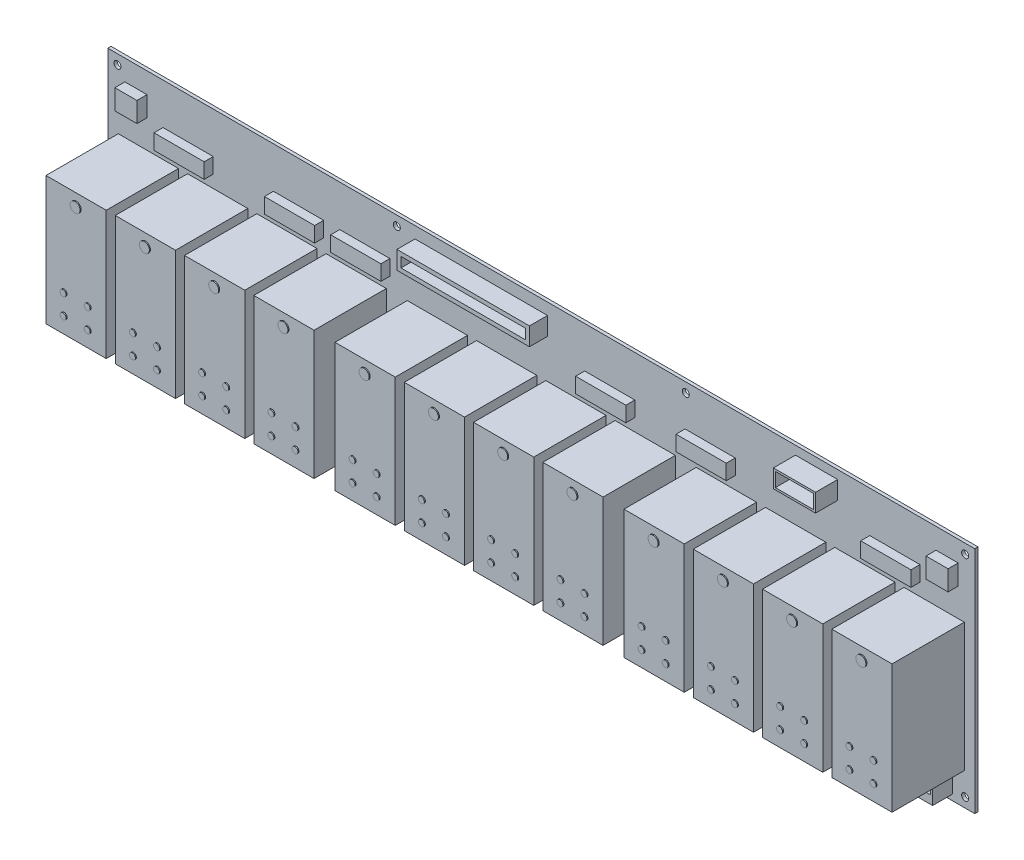
SolidWorks part; units mm, degrees
ref_plane "Front Plane" through (0, 0, 0) normal (0, 0, 1) x (1, 0, 0)
ref_plane "Top Plane" through (0, 0, 0) normal (0, 1, 0) x (1, 0, 0)
ref_plane "Right Plane" through (0, 0, 0) normal (1, 0, 0) x (0, 0, -1)
sketch "Sketch1" plane through (0, 0, 0) normal (0, 0, 1) x (1, 0, 0)
  line L1 (0, 0) -> (431.8, 0)
  line L2 (0, 0) -> (0, 114.3)
  line L3 (0, 114.3) -> (431.8, 114.3)
  line L4 (431.8, 0) -> (431.8, 114.3)
extrude "PCB" add sketch "Sketch1" along normal blind 1.6
ref_plane "Plane_z1_6" through (0, 0, 1.6) normal (0, 0, 1) x (1, 0, 0)
sketch "Sketch2" plane through (0, 0, 1.6) normal (0, 0, 1) x (1, 0, 0)
  line L1 (27.5, 86.2) -> (52.5, 86.2)
  line L2 (27.5, 86.2) -> (27.5, 93.8)
  line L3 (27.5, 93.8) -> (52.5, 93.8)
  line L4 (52.5, 86.2) -> (52.5, 93.8)
  line L6 (82.5, 86.2) -> (107.5, 86.2)
  line L7 (82.5, 86.2) -> (82.5, 93.8)
  line L8 (82.5, 93.8) -> (107.5, 93.8)
  line L9 (107.5, 86.2) -> (107.5, 93.8)
  line L11 (115.5, 86.2) -> (140.5, 86.2)
  line L12 (115.5, 86.2) -> (115.5, 93.8)
  line L13 (115.5, 93.8) -> (140.5, 93.8)
  line L14 (140.5, 86.2) -> (140.5, 93.8)
  line L16 (237.5, 86.2) -> (262.5, 86.2)
  line L17 (237.5, 86.2) -> (237.5, 93.8)
  line L18 (237.5, 93.8) -> (262.5, 93.8)
  line L19 (262.5, 86.2) -> (262.5, 93.8)
  line L21 (287.5, 86.2) -> (312.5, 86.2)
  line L22 (287.5, 86.2) -> (287.5, 93.8)
  line L23 (287.5, 93.8) -> (312.5, 93.8)
  line L24 (312.5, 86.2) -> (312.5, 93.8)
  line L26 (379.5, 86.2) -> (404.5, 86.2)
  line L27 (379.5, 86.2) -> (379.5, 93.8)
  line L28 (379.5, 93.8) -> (404.5, 93.8)
  line L29 (404.5, 86.2) -> (404.5, 93.8)
extrude "Body00" add sketch "Sketch2" along normal blind 4.5
sketch "Sketch3" plane through (0, 0, 1.6) normal (0, 0, 1) x (1, 0, 0)
  line L1 (8.5, 94) -> (19.5, 94)
  line L2 (8.5, 94) -> (8.5, 104)
  line L3 (8.5, 104) -> (19.5, 104)
  line L4 (19.5, 94) -> (19.5, 104)
  line L6 (412.5, 94) -> (423.5, 94)
  line L7 (412.5, 94) -> (412.5, 104)
  line L8 (412.5, 104) -> (423.5, 104)
  line L9 (423.5, 94) -> (423.5, 104)
extrude "Body01" add sketch "Sketch3" along normal blind 5
sketch "Sketch4" plane through (0, 0, 1.6) normal (0, 0, 1) x (1, 0, 0)
  line L1 (153, 99.5) -> (219, 99.5)
  line L2 (153, 99.5) -> (153, 108.5)
  line L3 (153, 108.5) -> (219, 108.5)
  line L4 (219, 99.5) -> (219, 108.5)
extrude "Body02" add sketch "Sketch4" along normal blind 9
sketch "Sketch5" plane through (0, 0, 1.6) normal (0, 0, 1) x (1, 0, 0)
  line L1 (11.007, 3) -> (132.927, 3)
  line L2 (11.007, 3) -> (11.007, 12)
  line L3 (11.007, 12) -> (132.927, 12)
  line L4 (132.927, 3) -> (132.927, 12)
  line L6 (154.94, 3) -> (276.86, 3)
  line L7 (154.94, 3) -> (154.94, 12)
  line L8 (154.94, 12) -> (276.86, 12)
  line L9 (276.86, 3) -> (276.86, 12)
  line L11 (298.873, 3) -> (420.793, 3)
  line L12 (298.873, 3) -> (298.873, 12)
  line L13 (298.873, 12) -> (420.793, 12)
  line L14 (420.793, 3) -> (420.793, 12)
extrude "Body03" add sketch "Sketch5" along normal blind 10
sketch "Sketch6" plane through (0, 0, 1.6) normal (0, 0, 1) x (1, 0, 0)
  line L1 (342.5, 101) -> (363.5, 101)
  line L2 (342.5, 101) -> (342.5, 110)
  line L3 (342.5, 110) -> (363.5, 110)
  line L4 (363.5, 101) -> (363.5, 110)
extrude "Body04" add sketch "Sketch6" along normal blind 11
sketch "Sketch7" plane through (0, 0, 1.6) normal (0, 0, 1) x (1, 0, 0)
  line L1 (5.217, 16) -> (35.217, 16)
  line L2 (5.217, 16) -> (5.217, 80)
  line L3 (5.217, 80) -> (35.217, 80)
  line L4 (35.217, 16) -> (35.217, 80)
  line L6 (39.717, 16) -> (69.717, 16)
  line L7 (39.717, 16) -> (39.717, 80)
  line L8 (39.717, 80) -> (69.717, 80)
  line L9 (69.717, 16) -> (69.717, 80)
  line L11 (74.217, 16) -> (104.217, 16)
  line L12 (74.217, 16) -> (74.217, 80)
  line L13 (74.217, 80) -> (104.217, 80)
  line L14 (104.217, 16) -> (104.217, 80)
  line L16 (108.717, 16) -> (138.717, 16)
  line L17 (108.717, 16) -> (108.717, 80)
  line L18 (108.717, 80) -> (138.717, 80)
  line L19 (138.717, 16) -> (138.717, 80)
  line L21 (149.15, 16) -> (179.15, 16)
  line L22 (149.15, 16) -> (149.15, 80)
  line L23 (149.15, 80) -> (179.15, 80)
  line L24 (179.15, 16) -> (179.15, 80)
  line L26 (183.65, 16) -> (213.65, 16)
  line L27 (183.65, 16) -> (183.65, 80)
  line L28 (183.65, 80) -> (213.65, 80)
  line L29 (213.65, 16) -> (213.65, 80)
  line L31 (218.15, 16) -> (248.15, 16)
  line L32 (218.15, 16) -> (218.15, 80)
  line L33 (218.15, 80) -> (248.15, 80)
  line L34 (248.15, 16) -> (248.15, 80)
  line L36 (252.65, 16) -> (282.65, 16)
  line L37 (252.65, 16) -> (252.65, 80)
  line L38 (252.65, 80) -> (282.65, 80)
  line L39 (282.65, 16) -> (282.65, 80)
  line L41 (293.083, 16) -> (323.083, 16)
  line L42 (293.083, 16) -> (293.083, 80)
  line L43 (293.083, 80) -> (323.083, 80)
  line L44 (323.083, 16) -> (323.083, 80)
  line L46 (327.583, 16) -> (357.583, 16)
  line L47 (327.583, 16) -> (327.583, 80)
  line L48 (327.583, 80) -> (357.583, 80)
  line L49 (357.583, 16) -> (357.583, 80)
  line L51 (362.083, 16) -> (392.083, 16)
  line L52 (362.083, 16) -> (362.083, 80)
  line L53 (362.083, 80) -> (392.083, 80)
  line L54 (392.083, 16) -> (392.083, 80)
  line L56 (396.583, 16) -> (426.583, 16)
  line L57 (396.583, 16) -> (396.583, 80)
  line L58 (396.583, 80) -> (426.583, 80)
  line L59 (426.583, 16) -> (426.583, 80)
extrude "Body05" add sketch "Sketch7" along normal blind 36
ref_plane "Plane_z37_6" through (0, 0, 37.6) normal (0, 0, 1) x (1, 0, 0)
sketch "Sketch8" plane through (0, 0, 37.6) normal (0, 0, 1) x (1, 0, 0)
  circle A0 centre (14.217, 24) radius 1.5
  circle A1 centre (14.217, 34) radius 1.5
  circle A2 centre (26.217, 24) radius 1.5
  circle A3 centre (26.217, 34) radius 1.5
  circle A4 centre (20.217, 74) radius 2.5
  circle A5 centre (48.717, 24) radius 1.5
  circle A6 centre (48.717, 34) radius 1.5
  circle A7 centre (60.717, 24) radius 1.5
  circle A8 centre (60.717, 34) radius 1.5
  circle A9 centre (54.717, 74) radius 2.5
  circle A10 centre (83.217, 24) radius 1.5
  circle A11 centre (83.217, 34) radius 1.5
  circle A12 centre (95.217, 24) radius 1.5
  circle A13 centre (95.217, 34) radius 1.5
  circle A14 centre (89.217, 74) radius 2.5
  circle A15 centre (117.717, 24) radius 1.5
  circle A16 centre (117.717, 34) radius 1.5
  circle A17 centre (129.717, 24) radius 1.5
  circle A18 centre (129.717, 34) radius 1.5
  circle A19 centre (123.717, 74) radius 2.5
  circle A20 centre (158.15, 24) radius 1.5
  circle A21 centre (158.15, 34) radius 1.5
  circle A22 centre (170.15, 24) radius 1.5
  circle A23 centre (170.15, 34) radius 1.5
  circle A24 centre (164.15, 74) radius 2.5
  circle A25 centre (192.65, 24) radius 1.5
  circle A26 centre (192.65, 34) radius 1.5
  circle A27 centre (204.65, 24) radius 1.5
  circle A28 centre (204.65, 34) radius 1.5
  circle A29 centre (198.65, 74) radius 2.5
  circle A30 centre (227.15, 24) radius 1.5
  circle A31 centre (227.15, 34) radius 1.5
  circle A32 centre (239.15, 24) radius 1.5
  circle A33 centre (239.15, 34) radius 1.5
  circle A34 centre (233.15, 74) radius 2.5
  circle A35 centre (261.65, 24) radius 1.5
  circle A36 centre (261.65, 34) radius 1.5
  circle A37 centre (273.65, 24) radius 1.5
  circle A38 centre (273.65, 34) radius 1.5
  circle A39 centre (267.65, 74) radius 2.5
  circle A40 centre (302.083, 24) radius 1.5
  circle A41 centre (302.083, 34) radius 1.5
  circle A42 centre (314.083, 24) radius 1.5
  circle A43 centre (314.083, 34) radius 1.5
  circle A44 centre (308.083, 74) radius 2.5
  circle A45 centre (336.583, 24) radius 1.5
  circle A46 centre (336.583, 34) radius 1.5
  circle A47 centre (348.583, 24) radius 1.5
  circle A48 centre (348.583, 34) radius 1.5
  circle A49 centre (342.583, 74) radius 2.5
  circle A50 centre (371.083, 24) radius 1.5
  circle A51 centre (371.083, 34) radius 1.5
  circle A52 centre (383.083, 24) radius 1.5
  circle A53 centre (383.083, 34) radius 1.5
  circle A54 centre (377.083, 74) radius 2.5
  circle A55 centre (405.583, 24) radius 1.5
  circle A56 centre (405.583, 34) radius 1.5
  circle A57 centre (417.583, 24) radius 1.5
  circle A58 centre (417.583, 34) radius 1.5
  circle A59 centre (411.583, 74) radius 2.5
extrude "Body06" add sketch "Sketch8" along normal blind 0.5
ref_plane "Plane_y7" through (0, 7, 0) normal (0, 1, 0) x (1, 0, 0)
sketch "Sketch9" plane through (0, 7, 0) normal (0, 1, 0) x (1, 0, 0)
  line L1 (11.947, -3.5) -> (15.147, -3.5)
  line L2 (11.947, -3.5) -> (11.947, -6.7)
  line L3 (11.947, -6.7) -> (15.147, -6.7)
  line L4 (15.147, -3.5) -> (15.147, -6.7)
  line L6 (17.027, -3.5) -> (20.227, -3.5)
  line L7 (17.027, -3.5) -> (17.027, -6.7)
  line L8 (17.027, -6.7) -> (20.227, -6.7)
  line L9 (20.227, -3.5) -> (20.227, -6.7)
  line L11 (22.107, -3.5) -> (25.307, -3.5)
  line L12 (22.107, -3.5) -> (22.107, -6.7)
  line L13 (22.107, -6.7) -> (25.307, -6.7)
  line L14 (25.307, -3.5) -> (25.307, -6.7)
  line L16 (27.187, -3.5) -> (30.387, -3.5)
  line L17 (27.187, -3.5) -> (27.187, -6.7)
  line L18 (27.187, -6.7) -> (30.387, -6.7)
  line L19 (30.387, -3.5) -> (30.387, -6.7)
  line L21 (32.267, -3.5) -> (35.467, -3.5)
  line L22 (32.267, -3.5) -> (32.267, -6.7)
  line L23 (32.267, -6.7) -> (35.467, -6.7)
  line L24 (35.467, -3.5) -> (35.467, -6.7)
  line L26 (37.347, -3.5) -> (40.547, -3.5)
  line L27 (37.347, -3.5) -> (37.347, -6.7)
  line L28 (37.347, -6.7) -> (40.547, -6.7)
  line L29 (40.547, -3.5) -> (40.547, -6.7)
  line L31 (42.427, -3.5) -> (45.627, -3.5)
  line L32 (42.427, -3.5) -> (42.427, -6.7)
  line L33 (42.427, -6.7) -> (45.627, -6.7)
  line L34 (45.627, -3.5) -> (45.627, -6.7)
  line L36 (47.507, -3.5) -> (50.707, -3.5)
  line L37 (47.507, -3.5) -> (47.507, -6.7)
  line L38 (47.507, -6.7) -> (50.707, -6.7)
  line L39 (50.707, -3.5) -> (50.707, -6.7)
  line L41 (52.587, -3.5) -> (55.787, -3.5)
  line L42 (52.587, -3.5) -> (52.587, -6.7)
  line L43 (52.587, -6.7) -> (55.787, -6.7)
  line L44 (55.787, -3.5) -> (55.787, -6.7)
  line L46 (57.667, -3.5) -> (60.867, -3.5)
  line L47 (57.667, -3.5) -> (57.667, -6.7)
  line L48 (57.667, -6.7) -> (60.867, -6.7)
  line L49 (60.867, -3.5) -> (60.867, -6.7)
  line L51 (62.747, -3.5) -> (65.947, -3.5)
  line L52 (62.747, -3.5) -> (62.747, -6.7)
  line L53 (62.747, -6.7) -> (65.947, -6.7)
  line L54 (65.947, -3.5) -> (65.947, -6.7)
  line L56 (67.827, -3.5) -> (71.027, -3.5)
  line L57 (67.827, -3.5) -> (67.827, -6.7)
  line L58 (67.827, -6.7) -> (71.027, -6.7)
  line L59 (71.027, -3.5) -> (71.027, -6.7)
  line L61 (72.907, -3.5) -> (76.107, -3.5)
  line L62 (72.907, -3.5) -> (72.907, -6.7)
  line L63 (72.907, -6.7) -> (76.107, -6.7)
  line L64 (76.107, -3.5) -> (76.107, -6.7)
  line L66 (77.987, -3.5) -> (81.187, -3.5)
  line L67 (77.987, -3.5) -> (77.987, -6.7)
  line L68 (77.987, -6.7) -> (81.187, -6.7)
  line L69 (81.187, -3.5) -> (81.187, -6.7)
  line L71 (83.067, -3.5) -> (86.267, -3.5)
  line L72 (83.067, -3.5) -> (83.067, -6.7)
  line L73 (83.067, -6.7) -> (86.267, -6.7)
  line L74 (86.267, -3.5) -> (86.267, -6.7)
  line L76 (88.147, -3.5) -> (91.347, -3.5)
  line L77 (88.147, -3.5) -> (88.147, -6.7)
  line L78 (88.147, -6.7) -> (91.347, -6.7)
  line L79 (91.347, -3.5) -> (91.347, -6.7)
  line L81 (93.227, -3.5) -> (96.427, -3.5)
  line L82 (93.227, -3.5) -> (93.227, -6.7)
  line L83 (93.227, -6.7) -> (96.427, -6.7)
  line L84 (96.427, -3.5) -> (96.427, -6.7)
  line L86 (98.307, -3.5) -> (101.507, -3.5)
  line L87 (98.307, -3.5) -> (98.307, -6.7)
  line L88 (98.307, -6.7) -> (101.507, -6.7)
  line L89 (101.507, -3.5) -> (101.507, -6.7)
  line L91 (103.387, -3.5) -> (106.587, -3.5)
  line L92 (103.387, -3.5) -> (103.387, -6.7)
  line L93 (103.387, -6.7) -> (106.587, -6.7)
  line L94 (106.587, -3.5) -> (106.587, -6.7)
  line L96 (108.467, -3.5) -> (111.667, -3.5)
  line L97 (108.467, -3.5) -> (108.467, -6.7)
  line L98 (108.467, -6.7) -> (111.667, -6.7)
  line L99 (111.667, -3.5) -> (111.667, -6.7)
  line L101 (113.547, -3.5) -> (116.747, -3.5)
  line L102 (113.547, -3.5) -> (113.547, -6.7)
  line L103 (113.547, -6.7) -> (116.747, -6.7)
  line L104 (116.747, -3.5) -> (116.747, -6.7)
  line L106 (118.627, -3.5) -> (121.827, -3.5)
  line L107 (118.627, -3.5) -> (118.627, -6.7)
  line L108 (118.627, -6.7) -> (121.827, -6.7)
  line L109 (121.827, -3.5) -> (121.827, -6.7)
  line L111 (123.707, -3.5) -> (126.907, -3.5)
  line L112 (123.707, -3.5) -> (123.707, -6.7)
  line L113 (123.707, -6.7) -> (126.907, -6.7)
  line L114 (126.907, -3.5) -> (126.907, -6.7)
  line L116 (128.787, -3.5) -> (131.987, -3.5)
  line L117 (128.787, -3.5) -> (128.787, -6.7)
  line L118 (128.787, -6.7) -> (131.987, -6.7)
  line L119 (131.987, -3.5) -> (131.987, -6.7)
  line L121 (155.88, -3.5) -> (159.08, -3.5)
  line L122 (155.88, -3.5) -> (155.88, -6.7)
  line L123 (155.88, -6.7) -> (159.08, -6.7)
  line L124 (159.08, -3.5) -> (159.08, -6.7)
  line L126 (160.96, -3.5) -> (164.16, -3.5)
  line L127 (160.96, -3.5) -> (160.96, -6.7)
  line L128 (160.96, -6.7) -> (164.16, -6.7)
  line L129 (164.16, -3.5) -> (164.16, -6.7)
  line L131 (166.04, -3.5) -> (169.24, -3.5)
  line L132 (166.04, -3.5) -> (166.04, -6.7)
  line L133 (166.04, -6.7) -> (169.24, -6.7)
  line L134 (169.24, -3.5) -> (169.24, -6.7)
  line L136 (171.12, -3.5) -> (174.32, -3.5)
  line L137 (171.12, -3.5) -> (171.12, -6.7)
  line L138 (171.12, -6.7) -> (174.32, -6.7)
  line L139 (174.32, -3.5) -> (174.32, -6.7)
  line L141 (176.2, -3.5) -> (179.4, -3.5)
  line L142 (176.2, -3.5) -> (176.2, -6.7)
  line L143 (176.2, -6.7) -> (179.4, -6.7)
  line L144 (179.4, -3.5) -> (179.4, -6.7)
  line L146 (181.28, -3.5) -> (184.48, -3.5)
  line L147 (181.28, -3.5) -> (181.28, -6.7)
  line L148 (181.28, -6.7) -> (184.48, -6.7)
  line L149 (184.48, -3.5) -> (184.48, -6.7)
  line L151 (186.36, -3.5) -> (189.56, -3.5)
  line L152 (186.36, -3.5) -> (186.36, -6.7)
  line L153 (186.36, -6.7) -> (189.56, -6.7)
  line L154 (189.56, -3.5) -> (189.56, -6.7)
  line L156 (191.44, -3.5) -> (194.64, -3.5)
  line L157 (191.44, -3.5) -> (191.44, -6.7)
  line L158 (191.44, -6.7) -> (194.64, -6.7)
  line L159 (194.64, -3.5) -> (194.64, -6.7)
  line L161 (196.52, -3.5) -> (199.72, -3.5)
  line L162 (196.52, -3.5) -> (196.52, -6.7)
  line L163 (196.52, -6.7) -> (199.72, -6.7)
  line L164 (199.72, -3.5) -> (199.72, -6.7)
  line L166 (201.6, -3.5) -> (204.8, -3.5)
  line L167 (201.6, -3.5) -> (201.6, -6.7)
  line L168 (201.6, -6.7) -> (204.8, -6.7)
  line L169 (204.8, -3.5) -> (204.8, -6.7)
  line L171 (206.68, -3.5) -> (209.88, -3.5)
  line L172 (206.68, -3.5) -> (206.68, -6.7)
  line L173 (206.68, -6.7) -> (209.88, -6.7)
  line L174 (209.88, -3.5) -> (209.88, -6.7)
  line L176 (211.76, -3.5) -> (214.96, -3.5)
  line L177 (211.76, -3.5) -> (211.76, -6.7)
  line L178 (211.76, -6.7) -> (214.96, -6.7)
  line L179 (214.96, -3.5) -> (214.96, -6.7)
  line L181 (216.84, -3.5) -> (220.04, -3.5)
  line L182 (216.84, -3.5) -> (216.84, -6.7)
  line L183 (216.84, -6.7) -> (220.04, -6.7)
  line L184 (220.04, -3.5) -> (220.04, -6.7)
  line L186 (221.92, -3.5) -> (225.12, -3.5)
  line L187 (221.92, -3.5) -> (221.92, -6.7)
  line L188 (221.92, -6.7) -> (225.12, -6.7)
  line L189 (225.12, -3.5) -> (225.12, -6.7)
  line L191 (227, -3.5) -> (230.2, -3.5)
  line L192 (227, -3.5) -> (227, -6.7)
  line L193 (227, -6.7) -> (230.2, -6.7)
  line L194 (230.2, -3.5) -> (230.2, -6.7)
  line L196 (232.08, -3.5) -> (235.28, -3.5)
  line L197 (232.08, -3.5) -> (232.08, -6.7)
  line L198 (232.08, -6.7) -> (235.28, -6.7)
  line L199 (235.28, -3.5) -> (235.28, -6.7)
  line L201 (237.16, -3.5) -> (240.36, -3.5)
  line L202 (237.16, -3.5) -> (237.16, -6.7)
  line L203 (237.16, -6.7) -> (240.36, -6.7)
  line L204 (240.36, -3.5) -> (240.36, -6.7)
  line L206 (242.24, -3.5) -> (245.44, -3.5)
  line L207 (242.24, -3.5) -> (242.24, -6.7)
  line L208 (242.24, -6.7) -> (245.44, -6.7)
  line L209 (245.44, -3.5) -> (245.44, -6.7)
  line L211 (247.32, -3.5) -> (250.52, -3.5)
  line L212 (247.32, -3.5) -> (247.32, -6.7)
  line L213 (247.32, -6.7) -> (250.52, -6.7)
  line L214 (250.52, -3.5) -> (250.52, -6.7)
  line L216 (252.4, -3.5) -> (255.6, -3.5)
  line L217 (252.4, -3.5) -> (252.4, -6.7)
  line L218 (252.4, -6.7) -> (255.6, -6.7)
  line L219 (255.6, -3.5) -> (255.6, -6.7)
  line L221 (257.48, -3.5) -> (260.68, -3.5)
  line L222 (257.48, -3.5) -> (257.48, -6.7)
  line L223 (257.48, -6.7) -> (260.68, -6.7)
  line L224 (260.68, -3.5) -> (260.68, -6.7)
  line L226 (262.56, -3.5) -> (265.76, -3.5)
  line L227 (262.56, -3.5) -> (262.56, -6.7)
  line L228 (262.56, -6.7) -> (265.76, -6.7)
  line L229 (265.76, -3.5) -> (265.76, -6.7)
  line L231 (267.64, -3.5) -> (270.84, -3.5)
  line L232 (267.64, -3.5) -> (267.64, -6.7)
  line L233 (267.64, -6.7) -> (270.84, -6.7)
  line L234 (270.84, -3.5) -> (270.84, -6.7)
  line L236 (272.72, -3.5) -> (275.92, -3.5)
  line L237 (272.72, -3.5) -> (272.72, -6.7)
  line L238 (272.72, -6.7) -> (275.92, -6.7)
  line L239 (275.92, -3.5) -> (275.92, -6.7)
  line L241 (299.813, -3.5) -> (303.013, -3.5)
  line L242 (299.813, -3.5) -> (299.813, -6.7)
  line L243 (299.813, -6.7) -> (303.013, -6.7)
  line L244 (303.013, -3.5) -> (303.013, -6.7)
  line L246 (304.893, -3.5) -> (308.093, -3.5)
  line L247 (304.893, -3.5) -> (304.893, -6.7)
  line L248 (304.893, -6.7) -> (308.093, -6.7)
  line L249 (308.093, -3.5) -> (308.093, -6.7)
  line L251 (309.973, -3.5) -> (313.173, -3.5)
  line L252 (309.973, -3.5) -> (309.973, -6.7)
  line L253 (309.973, -6.7) -> (313.173, -6.7)
  line L254 (313.173, -3.5) -> (313.173, -6.7)
  line L256 (315.053, -3.5) -> (318.253, -3.5)
  line L257 (315.053, -3.5) -> (315.053, -6.7)
  line L258 (315.053, -6.7) -> (318.253, -6.7)
  line L259 (318.253, -3.5) -> (318.253, -6.7)
  line L261 (320.133, -3.5) -> (323.333, -3.5)
  line L262 (320.133, -3.5) -> (320.133, -6.7)
  line L263 (320.133, -6.7) -> (323.333, -6.7)
  line L264 (323.333, -3.5) -> (323.333, -6.7)
  line L266 (325.213, -3.5) -> (328.413, -3.5)
  line L267 (325.213, -3.5) -> (325.213, -6.7)
  line L268 (325.213, -6.7) -> (328.413, -6.7)
  line L269 (328.413, -3.5) -> (328.413, -6.7)
  line L271 (330.293, -3.5) -> (333.493, -3.5)
  line L272 (330.293, -3.5) -> (330.293, -6.7)
  line L273 (330.293, -6.7) -> (333.493, -6.7)
  line L274 (333.493, -3.5) -> (333.493, -6.7)
  line L276 (335.373, -3.5) -> (338.573, -3.5)
  line L277 (335.373, -3.5) -> (335.373, -6.7)
  line L278 (335.373, -6.7) -> (338.573, -6.7)
  line L279 (338.573, -3.5) -> (338.573, -6.7)
  line L281 (340.453, -3.5) -> (343.653, -3.5)
  line L282 (340.453, -3.5) -> (340.453, -6.7)
  line L283 (340.453, -6.7) -> (343.653, -6.7)
  line L284 (343.653, -3.5) -> (343.653, -6.7)
  line L286 (345.533, -3.5) -> (348.733, -3.5)
  line L287 (345.533, -3.5) -> (345.533, -6.7)
  line L288 (345.533, -6.7) -> (348.733, -6.7)
  line L289 (348.733, -3.5) -> (348.733, -6.7)
  line L291 (350.613, -3.5) -> (353.813, -3.5)
  line L292 (350.613, -3.5) -> (350.613, -6.7)
  line L293 (350.613, -6.7) -> (353.813, -6.7)
  line L294 (353.813, -3.5) -> (353.813, -6.7)
  line L296 (355.693, -3.5) -> (358.893, -3.5)
  line L297 (355.693, -3.5) -> (355.693, -6.7)
  line L298 (355.693, -6.7) -> (358.893, -6.7)
  line L299 (358.893, -3.5) -> (358.893, -6.7)
  line L301 (360.773, -3.5) -> (363.973, -3.5)
  line L302 (360.773, -3.5) -> (360.773, -6.7)
  line L303 (360.773, -6.7) -> (363.973, -6.7)
  line L304 (363.973, -3.5) -> (363.973, -6.7)
  line L306 (365.853, -3.5) -> (369.053, -3.5)
  line L307 (365.853, -3.5) -> (365.853, -6.7)
  line L308 (365.853, -6.7) -> (369.053, -6.7)
  line L309 (369.053, -3.5) -> (369.053, -6.7)
  line L311 (370.933, -3.5) -> (374.133, -3.5)
  line L312 (370.933, -3.5) -> (370.933, -6.7)
  line L313 (370.933, -6.7) -> (374.133, -6.7)
  line L314 (374.133, -3.5) -> (374.133, -6.7)
  line L316 (376.013, -3.5) -> (379.213, -3.5)
  line L317 (376.013, -3.5) -> (376.013, -6.7)
  line L318 (376.013, -6.7) -> (379.213, -6.7)
  line L319 (379.213, -3.5) -> (379.213, -6.7)
  line L321 (381.093, -3.5) -> (384.293, -3.5)
  line L322 (381.093, -3.5) -> (381.093, -6.7)
  line L323 (381.093, -6.7) -> (384.293, -6.7)
  line L324 (384.293, -3.5) -> (384.293, -6.7)
  line L326 (386.173, -3.5) -> (389.373, -3.5)
  line L327 (386.173, -3.5) -> (386.173, -6.7)
  line L328 (386.173, -6.7) -> (389.373, -6.7)
  line L329 (389.373, -3.5) -> (389.373, -6.7)
  line L331 (391.253, -3.5) -> (394.453, -3.5)
  line L332 (391.253, -3.5) -> (391.253, -6.7)
  line L333 (391.253, -6.7) -> (394.453, -6.7)
  line L334 (394.453, -3.5) -> (394.453, -6.7)
  line L336 (396.333, -3.5) -> (399.533, -3.5)
  line L337 (396.333, -3.5) -> (396.333, -6.7)
  line L338 (396.333, -6.7) -> (399.533, -6.7)
  line L339 (399.533, -3.5) -> (399.533, -6.7)
  line L341 (401.413, -3.5) -> (404.613, -3.5)
  line L342 (401.413, -3.5) -> (401.413, -6.7)
  line L343 (401.413, -6.7) -> (404.613, -6.7)
  line L344 (404.613, -3.5) -> (404.613, -6.7)
  line L346 (406.493, -3.5) -> (409.693, -3.5)
  line L347 (406.493, -3.5) -> (406.493, -6.7)
  line L348 (406.493, -6.7) -> (409.693, -6.7)
  line L349 (409.693, -3.5) -> (409.693, -6.7)
  line L351 (411.573, -3.5) -> (414.773, -3.5)
  line L352 (411.573, -3.5) -> (411.573, -6.7)
  line L353 (411.573, -6.7) -> (414.773, -6.7)
  line L354 (414.773, -3.5) -> (414.773, -6.7)
  line L356 (416.653, -3.5) -> (419.853, -3.5)
  line L357 (416.653, -3.5) -> (416.653, -6.7)
  line L358 (416.653, -6.7) -> (419.853, -6.7)
  line L359 (419.853, -3.5) -> (419.853, -6.7)
extrude "Cut00" cut sketch "Sketch9" against normal blind 4
ref_plane "Plane_z10_6" through (0, 0, 10.6) normal (0, 0, 1) x (1, 0, 0)
sketch "Sketch10" plane through (0, 0, 10.6) normal (0, 0, 1) x (1, 0, 0)
  line L1 (155, 101.5) -> (217, 101.5)
  line L2 (155, 101.5) -> (155, 106.5)
  line L3 (155, 106.5) -> (217, 106.5)
  line L4 (217, 101.5) -> (217, 106.5)
extrude "Cut01" cut sketch "Sketch10" against normal blind 7
ref_plane "Plane_z11_6" through (0, 0, 11.6) normal (0, 0, 1) x (1, 0, 0)
sketch "Sketch11" plane through (0, 0, 11.6) normal (0, 0, 1) x (1, 0, 0)
  line L1 (12.147, 7.1) -> (14.947, 7.1)
  line L2 (12.147, 7.1) -> (12.147, 9.9)
  line L3 (12.147, 9.9) -> (14.947, 9.9)
  line L4 (14.947, 7.1) -> (14.947, 9.9)
  line L6 (17.227, 7.1) -> (20.027, 7.1)
  line L7 (17.227, 7.1) -> (17.227, 9.9)
  line L8 (17.227, 9.9) -> (20.027, 9.9)
  line L9 (20.027, 7.1) -> (20.027, 9.9)
  line L11 (22.307, 7.1) -> (25.107, 7.1)
  line L12 (22.307, 7.1) -> (22.307, 9.9)
  line L13 (22.307, 9.9) -> (25.107, 9.9)
  line L14 (25.107, 7.1) -> (25.107, 9.9)
  line L16 (27.387, 7.1) -> (30.187, 7.1)
  line L17 (27.387, 7.1) -> (27.387, 9.9)
  line L18 (27.387, 9.9) -> (30.187, 9.9)
  line L19 (30.187, 7.1) -> (30.187, 9.9)
  line L21 (32.467, 7.1) -> (35.267, 7.1)
  line L22 (32.467, 7.1) -> (32.467, 9.9)
  line L23 (32.467, 9.9) -> (35.267, 9.9)
  line L24 (35.267, 7.1) -> (35.267, 9.9)
  line L26 (37.547, 7.1) -> (40.347, 7.1)
  line L27 (37.547, 7.1) -> (37.547, 9.9)
  line L28 (37.547, 9.9) -> (40.347, 9.9)
  line L29 (40.347, 7.1) -> (40.347, 9.9)
  line L31 (42.627, 7.1) -> (45.427, 7.1)
  line L32 (42.627, 7.1) -> (42.627, 9.9)
  line L33 (42.627, 9.9) -> (45.427, 9.9)
  line L34 (45.427, 7.1) -> (45.427, 9.9)
  line L36 (47.707, 7.1) -> (50.507, 7.1)
  line L37 (47.707, 7.1) -> (47.707, 9.9)
  line L38 (47.707, 9.9) -> (50.507, 9.9)
  line L39 (50.507, 7.1) -> (50.507, 9.9)
  line L41 (52.787, 7.1) -> (55.587, 7.1)
  line L42 (52.787, 7.1) -> (52.787, 9.9)
  line L43 (52.787, 9.9) -> (55.587, 9.9)
  line L44 (55.587, 7.1) -> (55.587, 9.9)
  line L46 (57.867, 7.1) -> (60.667, 7.1)
  line L47 (57.867, 7.1) -> (57.867, 9.9)
  line L48 (57.867, 9.9) -> (60.667, 9.9)
  line L49 (60.667, 7.1) -> (60.667, 9.9)
  line L51 (62.947, 7.1) -> (65.747, 7.1)
  line L52 (62.947, 7.1) -> (62.947, 9.9)
  line L53 (62.947, 9.9) -> (65.747, 9.9)
  line L54 (65.747, 7.1) -> (65.747, 9.9)
  line L56 (68.027, 7.1) -> (70.827, 7.1)
  line L57 (68.027, 7.1) -> (68.027, 9.9)
  line L58 (68.027, 9.9) -> (70.827, 9.9)
  line L59 (70.827, 7.1) -> (70.827, 9.9)
  line L61 (73.107, 7.1) -> (75.907, 7.1)
  line L62 (73.107, 7.1) -> (73.107, 9.9)
  line L63 (73.107, 9.9) -> (75.907, 9.9)
  line L64 (75.907, 7.1) -> (75.907, 9.9)
  line L66 (78.187, 7.1) -> (80.987, 7.1)
  line L67 (78.187, 7.1) -> (78.187, 9.9)
  line L68 (78.187, 9.9) -> (80.987, 9.9)
  line L69 (80.987, 7.1) -> (80.987, 9.9)
  line L71 (83.267, 7.1) -> (86.067, 7.1)
  line L72 (83.267, 7.1) -> (83.267, 9.9)
  line L73 (83.267, 9.9) -> (86.067, 9.9)
  line L74 (86.067, 7.1) -> (86.067, 9.9)
  line L76 (88.347, 7.1) -> (91.147, 7.1)
  line L77 (88.347, 7.1) -> (88.347, 9.9)
  line L78 (88.347, 9.9) -> (91.147, 9.9)
  line L79 (91.147, 7.1) -> (91.147, 9.9)
  line L81 (93.427, 7.1) -> (96.227, 7.1)
  line L82 (93.427, 7.1) -> (93.427, 9.9)
  line L83 (93.427, 9.9) -> (96.227, 9.9)
  line L84 (96.227, 7.1) -> (96.227, 9.9)
  line L86 (98.507, 7.1) -> (101.307, 7.1)
  line L87 (98.507, 7.1) -> (98.507, 9.9)
  line L88 (98.507, 9.9) -> (101.307, 9.9)
  line L89 (101.307, 7.1) -> (101.307, 9.9)
  line L91 (103.587, 7.1) -> (106.387, 7.1)
  line L92 (103.587, 7.1) -> (103.587, 9.9)
  line L93 (103.587, 9.9) -> (106.387, 9.9)
  line L94 (106.387, 7.1) -> (106.387, 9.9)
  line L96 (108.667, 7.1) -> (111.467, 7.1)
  line L97 (108.667, 7.1) -> (108.667, 9.9)
  line L98 (108.667, 9.9) -> (111.467, 9.9)
  line L99 (111.467, 7.1) -> (111.467, 9.9)
  line L101 (113.747, 7.1) -> (116.547, 7.1)
  line L102 (113.747, 7.1) -> (113.747, 9.9)
  line L103 (113.747, 9.9) -> (116.547, 9.9)
  line L104 (116.547, 7.1) -> (116.547, 9.9)
  line L106 (118.827, 7.1) -> (121.627, 7.1)
  line L107 (118.827, 7.1) -> (118.827, 9.9)
  line L108 (118.827, 9.9) -> (121.627, 9.9)
  line L109 (121.627, 7.1) -> (121.627, 9.9)
  line L111 (123.907, 7.1) -> (126.707, 7.1)
  line L112 (123.907, 7.1) -> (123.907, 9.9)
  line L113 (123.907, 9.9) -> (126.707, 9.9)
  line L114 (126.707, 7.1) -> (126.707, 9.9)
  line L116 (128.987, 7.1) -> (131.787, 7.1)
  line L117 (128.987, 7.1) -> (128.987, 9.9)
  line L118 (128.987, 9.9) -> (131.787, 9.9)
  line L119 (131.787, 7.1) -> (131.787, 9.9)
  line L121 (156.08, 7.1) -> (158.88, 7.1)
  line L122 (156.08, 7.1) -> (156.08, 9.9)
  line L123 (156.08, 9.9) -> (158.88, 9.9)
  line L124 (158.88, 7.1) -> (158.88, 9.9)
  line L126 (161.16, 7.1) -> (163.96, 7.1)
  line L127 (161.16, 7.1) -> (161.16, 9.9)
  line L128 (161.16, 9.9) -> (163.96, 9.9)
  line L129 (163.96, 7.1) -> (163.96, 9.9)
  line L131 (166.24, 7.1) -> (169.04, 7.1)
  line L132 (166.24, 7.1) -> (166.24, 9.9)
  line L133 (166.24, 9.9) -> (169.04, 9.9)
  line L134 (169.04, 7.1) -> (169.04, 9.9)
  line L136 (171.32, 7.1) -> (174.12, 7.1)
  line L137 (171.32, 7.1) -> (171.32, 9.9)
  line L138 (171.32, 9.9) -> (174.12, 9.9)
  line L139 (174.12, 7.1) -> (174.12, 9.9)
  line L141 (176.4, 7.1) -> (179.2, 7.1)
  line L142 (176.4, 7.1) -> (176.4, 9.9)
  line L143 (176.4, 9.9) -> (179.2, 9.9)
  line L144 (179.2, 7.1) -> (179.2, 9.9)
  line L146 (181.48, 7.1) -> (184.28, 7.1)
  line L147 (181.48, 7.1) -> (181.48, 9.9)
  line L148 (181.48, 9.9) -> (184.28, 9.9)
  line L149 (184.28, 7.1) -> (184.28, 9.9)
  line L151 (186.56, 7.1) -> (189.36, 7.1)
  line L152 (186.56, 7.1) -> (186.56, 9.9)
  line L153 (186.56, 9.9) -> (189.36, 9.9)
  line L154 (189.36, 7.1) -> (189.36, 9.9)
  line L156 (191.64, 7.1) -> (194.44, 7.1)
  line L157 (191.64, 7.1) -> (191.64, 9.9)
  line L158 (191.64, 9.9) -> (194.44, 9.9)
  line L159 (194.44, 7.1) -> (194.44, 9.9)
  line L161 (196.72, 7.1) -> (199.52, 7.1)
  line L162 (196.72, 7.1) -> (196.72, 9.9)
  line L163 (196.72, 9.9) -> (199.52, 9.9)
  line L164 (199.52, 7.1) -> (199.52, 9.9)
  line L166 (201.8, 7.1) -> (204.6, 7.1)
  line L167 (201.8, 7.1) -> (201.8, 9.9)
  line L168 (201.8, 9.9) -> (204.6, 9.9)
  line L169 (204.6, 7.1) -> (204.6, 9.9)
  line L171 (206.88, 7.1) -> (209.68, 7.1)
  line L172 (206.88, 7.1) -> (206.88, 9.9)
  line L173 (206.88, 9.9) -> (209.68, 9.9)
  line L174 (209.68, 7.1) -> (209.68, 9.9)
  line L176 (211.96, 7.1) -> (214.76, 7.1)
  line L177 (211.96, 7.1) -> (211.96, 9.9)
  line L178 (211.96, 9.9) -> (214.76, 9.9)
  line L179 (214.76, 7.1) -> (214.76, 9.9)
  line L181 (217.04, 7.1) -> (219.84, 7.1)
  line L182 (217.04, 7.1) -> (217.04, 9.9)
  line L183 (217.04, 9.9) -> (219.84, 9.9)
  line L184 (219.84, 7.1) -> (219.84, 9.9)
  line L186 (222.12, 7.1) -> (224.92, 7.1)
  line L187 (222.12, 7.1) -> (222.12, 9.9)
  line L188 (222.12, 9.9) -> (224.92, 9.9)
  line L189 (224.92, 7.1) -> (224.92, 9.9)
  line L191 (227.2, 7.1) -> (230, 7.1)
  line L192 (227.2, 7.1) -> (227.2, 9.9)
  line L193 (227.2, 9.9) -> (230, 9.9)
  line L194 (230, 7.1) -> (230, 9.9)
  line L196 (232.28, 7.1) -> (235.08, 7.1)
  line L197 (232.28, 7.1) -> (232.28, 9.9)
  line L198 (232.28, 9.9) -> (235.08, 9.9)
  line L199 (235.08, 7.1) -> (235.08, 9.9)
  line L201 (237.36, 7.1) -> (240.16, 7.1)
  line L202 (237.36, 7.1) -> (237.36, 9.9)
  line L203 (237.36, 9.9) -> (240.16, 9.9)
  line L204 (240.16, 7.1) -> (240.16, 9.9)
  line L206 (242.44, 7.1) -> (245.24, 7.1)
  line L207 (242.44, 7.1) -> (242.44, 9.9)
  line L208 (242.44, 9.9) -> (245.24, 9.9)
  line L209 (245.24, 7.1) -> (245.24, 9.9)
  line L211 (247.52, 7.1) -> (250.32, 7.1)
  line L212 (247.52, 7.1) -> (247.52, 9.9)
  line L213 (247.52, 9.9) -> (250.32, 9.9)
  line L214 (250.32, 7.1) -> (250.32, 9.9)
  line L216 (252.6, 7.1) -> (255.4, 7.1)
  line L217 (252.6, 7.1) -> (252.6, 9.9)
  line L218 (252.6, 9.9) -> (255.4, 9.9)
  line L219 (255.4, 7.1) -> (255.4, 9.9)
  line L221 (257.68, 7.1) -> (260.48, 7.1)
  line L222 (257.68, 7.1) -> (257.68, 9.9)
  line L223 (257.68, 9.9) -> (260.48, 9.9)
  line L224 (260.48, 7.1) -> (260.48, 9.9)
  line L226 (262.76, 7.1) -> (265.56, 7.1)
  line L227 (262.76, 7.1) -> (262.76, 9.9)
  line L228 (262.76, 9.9) -> (265.56, 9.9)
  line L229 (265.56, 7.1) -> (265.56, 9.9)
  line L231 (267.84, 7.1) -> (270.64, 7.1)
  line L232 (267.84, 7.1) -> (267.84, 9.9)
  line L233 (267.84, 9.9) -> (270.64, 9.9)
  line L234 (270.64, 7.1) -> (270.64, 9.9)
  line L236 (272.92, 7.1) -> (275.72, 7.1)
  line L237 (272.92, 7.1) -> (272.92, 9.9)
  line L238 (272.92, 9.9) -> (275.72, 9.9)
  line L239 (275.72, 7.1) -> (275.72, 9.9)
  line L241 (300.013, 7.1) -> (302.813, 7.1)
  line L242 (300.013, 7.1) -> (300.013, 9.9)
  line L243 (300.013, 9.9) -> (302.813, 9.9)
  line L244 (302.813, 7.1) -> (302.813, 9.9)
  line L246 (305.093, 7.1) -> (307.893, 7.1)
  line L247 (305.093, 7.1) -> (305.093, 9.9)
  line L248 (305.093, 9.9) -> (307.893, 9.9)
  line L249 (307.893, 7.1) -> (307.893, 9.9)
  line L251 (310.173, 7.1) -> (312.973, 7.1)
  line L252 (310.173, 7.1) -> (310.173, 9.9)
  line L253 (310.173, 9.9) -> (312.973, 9.9)
  line L254 (312.973, 7.1) -> (312.973, 9.9)
  line L256 (315.253, 7.1) -> (318.053, 7.1)
  line L257 (315.253, 7.1) -> (315.253, 9.9)
  line L258 (315.253, 9.9) -> (318.053, 9.9)
  line L259 (318.053, 7.1) -> (318.053, 9.9)
  line L261 (320.333, 7.1) -> (323.133, 7.1)
  line L262 (320.333, 7.1) -> (320.333, 9.9)
  line L263 (320.333, 9.9) -> (323.133, 9.9)
  line L264 (323.133, 7.1) -> (323.133, 9.9)
  line L266 (325.413, 7.1) -> (328.213, 7.1)
  line L267 (325.413, 7.1) -> (325.413, 9.9)
  line L268 (325.413, 9.9) -> (328.213, 9.9)
  line L269 (328.213, 7.1) -> (328.213, 9.9)
  line L271 (330.493, 7.1) -> (333.293, 7.1)
  line L272 (330.493, 7.1) -> (330.493, 9.9)
  line L273 (330.493, 9.9) -> (333.293, 9.9)
  line L274 (333.293, 7.1) -> (333.293, 9.9)
  line L276 (335.573, 7.1) -> (338.373, 7.1)
  line L277 (335.573, 7.1) -> (335.573, 9.9)
  line L278 (335.573, 9.9) -> (338.373, 9.9)
  line L279 (338.373, 7.1) -> (338.373, 9.9)
  line L281 (340.653, 7.1) -> (343.453, 7.1)
  line L282 (340.653, 7.1) -> (340.653, 9.9)
  line L283 (340.653, 9.9) -> (343.453, 9.9)
  line L284 (343.453, 7.1) -> (343.453, 9.9)
  line L286 (345.733, 7.1) -> (348.533, 7.1)
  line L287 (345.733, 7.1) -> (345.733, 9.9)
  line L288 (345.733, 9.9) -> (348.533, 9.9)
  line L289 (348.533, 7.1) -> (348.533, 9.9)
  line L291 (350.813, 7.1) -> (353.613, 7.1)
  line L292 (350.813, 7.1) -> (350.813, 9.9)
  line L293 (350.813, 9.9) -> (353.613, 9.9)
  line L294 (353.613, 7.1) -> (353.613, 9.9)
  line L296 (355.893, 7.1) -> (358.693, 7.1)
  line L297 (355.893, 7.1) -> (355.893, 9.9)
  line L298 (355.893, 9.9) -> (358.693, 9.9)
  line L299 (358.693, 7.1) -> (358.693, 9.9)
  line L301 (360.973, 7.1) -> (363.773, 7.1)
  line L302 (360.973, 7.1) -> (360.973, 9.9)
  line L303 (360.973, 9.9) -> (363.773, 9.9)
  line L304 (363.773, 7.1) -> (363.773, 9.9)
  line L306 (366.053, 7.1) -> (368.853, 7.1)
  line L307 (366.053, 7.1) -> (366.053, 9.9)
  line L308 (366.053, 9.9) -> (368.853, 9.9)
  line L309 (368.853, 7.1) -> (368.853, 9.9)
  line L311 (371.133, 7.1) -> (373.933, 7.1)
  line L312 (371.133, 7.1) -> (371.133, 9.9)
  line L313 (371.133, 9.9) -> (373.933, 9.9)
  line L314 (373.933, 7.1) -> (373.933, 9.9)
  line L316 (376.213, 7.1) -> (379.013, 7.1)
  line L317 (376.213, 7.1) -> (376.213, 9.9)
  line L318 (376.213, 9.9) -> (379.013, 9.9)
  line L319 (379.013, 7.1) -> (379.013, 9.9)
  line L321 (381.293, 7.1) -> (384.093, 7.1)
  line L322 (381.293, 7.1) -> (381.293, 9.9)
  line L323 (381.293, 9.9) -> (384.093, 9.9)
  line L324 (384.093, 7.1) -> (384.093, 9.9)
  line L326 (386.373, 7.1) -> (389.173, 7.1)
  line L327 (386.373, 7.1) -> (386.373, 9.9)
  line L328 (386.373, 9.9) -> (389.173, 9.9)
  line L329 (389.173, 7.1) -> (389.173, 9.9)
  line L331 (391.453, 7.1) -> (394.253, 7.1)
  line L332 (391.453, 7.1) -> (391.453, 9.9)
  line L333 (391.453, 9.9) -> (394.253, 9.9)
  line L334 (394.253, 7.1) -> (394.253, 9.9)
  line L336 (396.533, 7.1) -> (399.333, 7.1)
  line L337 (396.533, 7.1) -> (396.533, 9.9)
  line L338 (396.533, 9.9) -> (399.333, 9.9)
  line L339 (399.333, 7.1) -> (399.333, 9.9)
  line L341 (401.613, 7.1) -> (404.413, 7.1)
  line L342 (401.613, 7.1) -> (401.613, 9.9)
  line L343 (401.613, 9.9) -> (404.413, 9.9)
  line L344 (404.413, 7.1) -> (404.413, 9.9)
  line L346 (406.693, 7.1) -> (409.493, 7.1)
  line L347 (406.693, 7.1) -> (406.693, 9.9)
  line L348 (406.693, 9.9) -> (409.493, 9.9)
  line L349 (409.493, 7.1) -> (409.493, 9.9)
  line L351 (411.773, 7.1) -> (414.573, 7.1)
  line L352 (411.773, 7.1) -> (411.773, 9.9)
  line L353 (411.773, 9.9) -> (414.573, 9.9)
  line L354 (414.573, 7.1) -> (414.573, 9.9)
  line L356 (416.853, 7.1) -> (419.653, 7.1)
  line L357 (416.853, 7.1) -> (416.853, 9.9)
  line L358 (416.853, 9.9) -> (419.653, 9.9)
  line L359 (419.653, 7.1) -> (419.653, 9.9)
extrude "Cut02" cut sketch "Sketch11" against normal blind 3
ref_plane "Plane_z12_6" through (0, 0, 12.6) normal (0, 0, 1) x (1, 0, 0)
sketch "Sketch12" plane through (0, 0, 12.6) normal (0, 0, 1) x (1, 0, 0)
  line L1 (343.5, 102) -> (362.5, 102)
  line L2 (343.5, 102) -> (343.5, 109)
  line L3 (343.5, 109) -> (362.5, 109)
  line L4 (362.5, 102) -> (362.5, 109)
extrude "Cut03" cut sketch "Sketch12" against normal blind 8
sketch "Sketch13" plane through (0, 0, 1.6) normal (0, 0, 1) x (1, 0, 0)
  circle A0 centre (4.8, 4.8) radius 1.75
  circle A1 centre (4.8, 109.5) radius 1.75
  circle A2 centre (143.933, 4.8) radius 1.75
  circle A3 centre (143.933, 109.5) radius 1.75
  circle A4 centre (287.867, 4.8) radius 1.75
  circle A5 centre (287.867, 109.5) radius 1.75
  circle A6 centre (427, 4.8) radius 1.75
  circle A7 centre (427, 109.5) radius 1.75
extrude "Holes" cut sketch "Sketch13" against normal blind 1.6
equation "\"pcb_t\"= 1.6mm"
equation "\"D1@PCB\" = \"pcb_t\""
